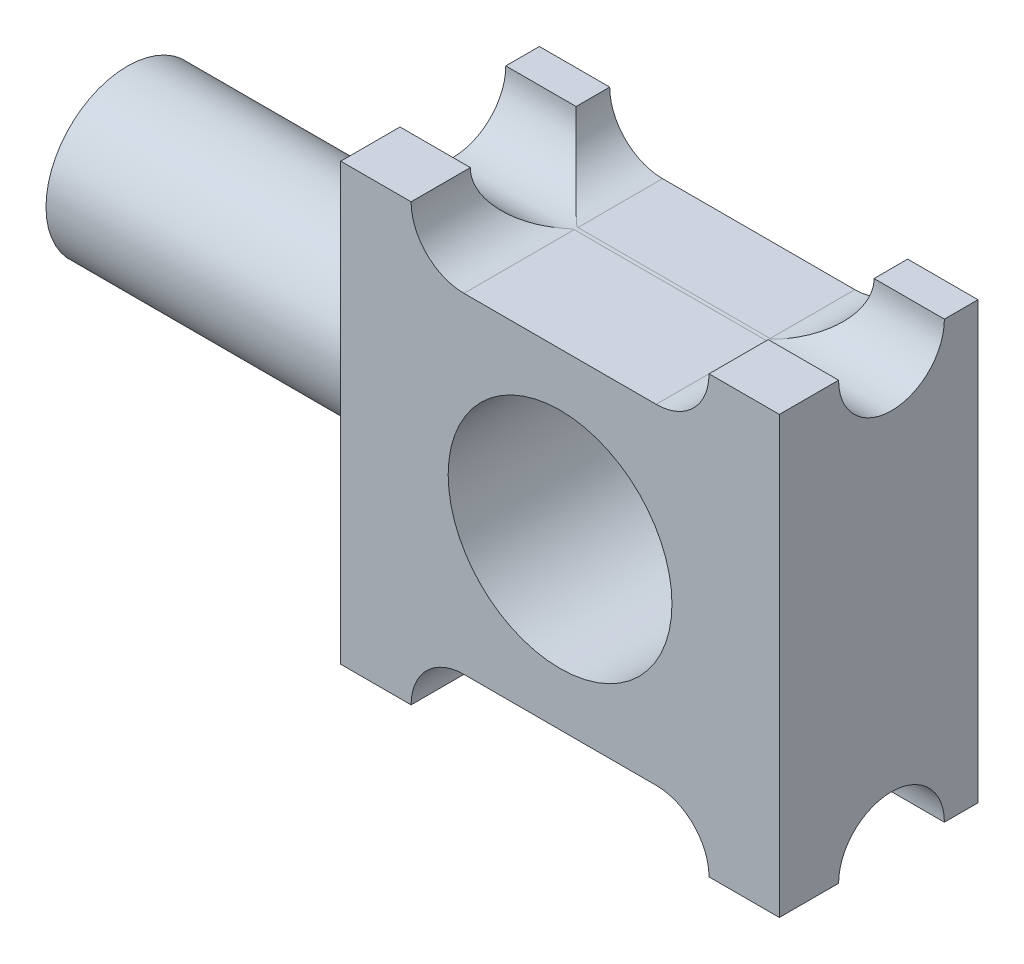
SolidWorks part; units mm, degrees
ref_plane "Front Plane" through (0, 0, 0) normal (0, 0, 1) x (1, 0, 0)
ref_plane "Top Plane" through (0, 0, 0) normal (0, 1, 0) x (1, 0, 0)
ref_plane "Right Plane" through (0, 0, 0) normal (1, 0, 0) x (0, 0, -1)
sketch "Sketch1" plane through (0, 0, 0) normal (0, 0, 1) x (1, 0, 0)
  line L1 (-6.8453, 6.8) -> (6.8453, 6.8)
  line L2 (-6.8453, 6.8) -> (-6.8453, -6.8)
  line L3 (-6.8453, -6.8) -> (6.8453, -6.8)
  line L4 (6.8453, 6.8) -> (6.8453, -6.8)
  line L5 (-6.8453, 6.8) -> (6.8453, -6.8) construction
  line L6 (-6.8453, -6.8) -> (6.8453, 6.8) construction
  point P0 (0, 0)
  dimension "D1" = 13.6906
  dimension "D2" = 13.6
extrude "Boss-Extrude1" add sketch "Sketch1" along normal blind 6.2
sketch "Sketch2" plane through (6.8453, 0, 0) normal (1, 0, 0) x (0, 0, -1)
  line L0 (-6.2, 6.8) -> (0, 6.8) construction
  line L1 (0, -6.8) -> (0, 6.8) construction
  line L2 (-6.2, 0) -> (0, 0) construction
  line L3 (-6.2, -6.8) -> (-6.2, 6.8) construction
  circle A0 centre (-2.7, 6.8) radius 1.651
  circle A1 centre (-2.7, -6.8) radius 1.651
  dimension "D2" = 3.302
  dimension "D1" = 2.7
extrude "Cut-Extrude1" cut sketch "Sketch2" against normal through all
sketch "Sketch3" plane through (0, 0, 6.2) normal (0, 0, 1) x (1, 0, 0)
  line L0 (6.8453, 6.8) -> (-6.8453, 6.8) construction
  line L1 (-3, 6.8) -> (3, 6.8)
  line L2 (-3, 6.8) -> (-3, 5.15)
  line L3 (-3, 5.15) -> (3, 5.15)
  line L4 (3, 6.8) -> (3, 5.15)
  line L5 (0, 5.15) -> (0, 7.1831) construction
  line L6 (-6.8453, 0) -> (0, 5.15) construction
  line L7 (-6.8453, 6.8) -> (-6.8453, -6.8) construction
  line L8 (0, 5.15) -> (6.8453, 0) construction
  line L9 (6.8453, -6.8) -> (6.8453, 6.8) construction
  line L10 (-6.8453, 0) -> (6.8453, 0) construction
  line L11 (0, -5.15) -> (6.8453, 0) construction
  line L12 (-6.8453, 0) -> (0, -5.15) construction
  line L13 (0, -5.15) -> (0, -7.1831) construction
  line L14 (3, -6.8) -> (3, -5.15)
  line L15 (-3, -5.15) -> (3, -5.15)
  line L16 (-3, -6.8) -> (-3, -5.15)
  line L17 (-3, -6.8) -> (3, -6.8)
  line L18 (-4.65, 6.8) -> (4.65, 6.8)
  line L19 (-3, -6.8) -> (3, -6.8)
  arc A0 (3, 5.15) -> (4.65, 6.8) centre (3, 6.8) ccw
  arc A1 (-3, 5.15) -> (-4.65, 6.8) centre (-3, 6.8) cw
  arc A2 (-3, -5.15) -> (-4.65, -6.8) centre (-3, -6.8) ccw
  arc A3 (3, -5.15) -> (4.65, -6.8) centre (3, -6.8) cw
  line M9 (6.8453, 6.8) -> (-6.8453, 6.8)
  line M11 (-6.8453, -6.8) -> (6.8453, -6.8)
  dimension "D2" = 1.65
  dimension "D1" = 1.65
  dimension "D3" = 6
extrude "Cut-Extrude2" cut sketch "Sketch3" against normal through all contours A1 L2 M9 | L4 L2 L3 M9 | L4 A0 M9 | A3 L14 M11 | L16 L14 L15 M11 | L16 A2 M11 region at (0, 5.975, 6.2) region at (-3.7003, 6.0997, 6.2) region at (3.7003, 6.0997, 6.2) region at (0, -5.975, 6.2) region at (3.7003, -6.0997, 6.2) region at (-3.7003, -6.0997, 6.2)
sketch "Sketch4" plane through (0, 0, 6.2) normal (0, 0, 1) x (1, 0, 0)
  circle A0 centre (0, 0) radius 3.4925
  dimension "D1" = 6.985
extrude "Cut-Extrude3" cut sketch "Sketch4" against normal through all
sketch "Sketch5" plane through (-6.8453, 0, 0) normal (-1, 0, 0) x (0, 0, 1)
  circle A0 centre (2.7, 0) radius 2.54
  dimension "D1" = 5.08
extrude "Boss-Extrude2" add sketch "Sketch5" along normal blind 10.16
